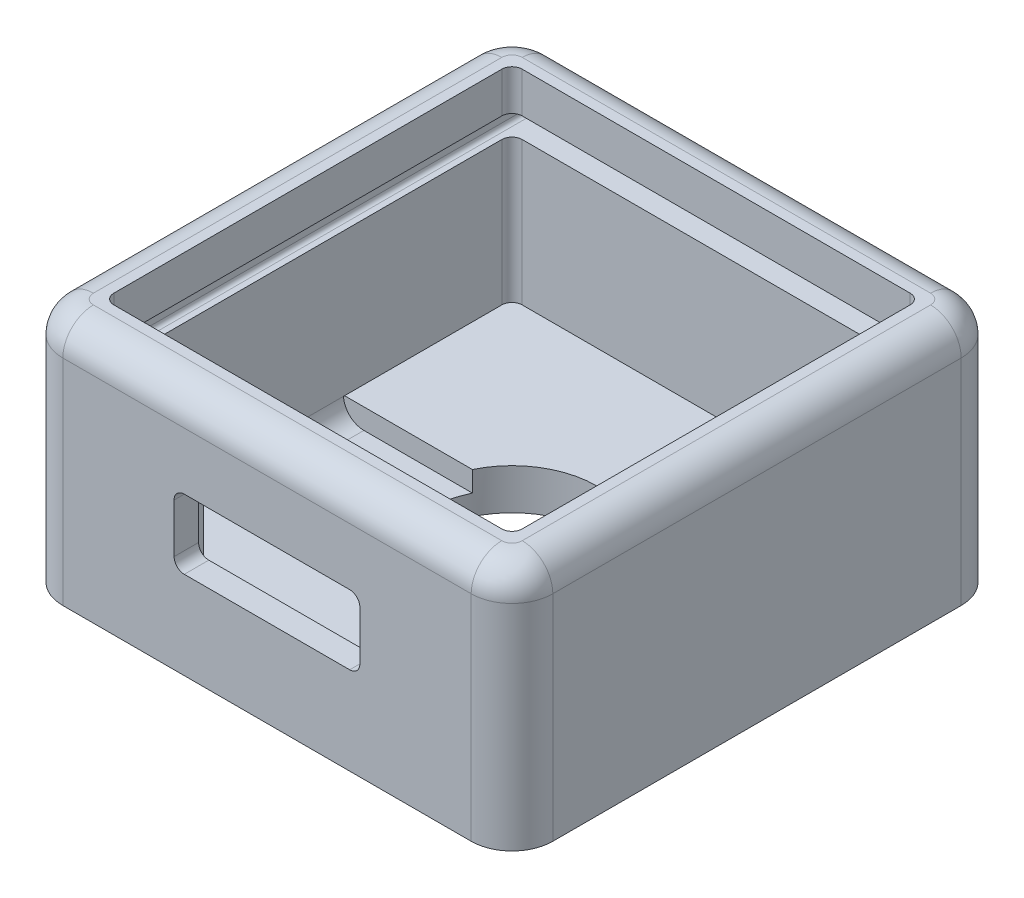
SolidWorks part; units mm, degrees
ref_plane "Front Plane" through (0, 0, 0) normal (0, 0, 1) x (1, 0, 0)
ref_plane "Top Plane" through (0, 0, 0) normal (0, 1, 0) x (1, 0, 0)
ref_plane "Right Plane" through (0, 0, 0) normal (1, 0, 0) x (0, 0, -1)
sketch "Sketch2" plane through (0, 0, 0) normal (0, 1, 0) x (1, 0, 0)
  line L1 (-10, -12) -> (10, -12)
  line L2 (-12, -10) -> (-12, 10)
  line L3 (-10, 12) -> (10, 12)
  line L4 (12, -10) -> (12, 10)
  line L5 (-12, -12) -> (12, 12) construction
  line L6 (-12, 12) -> (12, -12) construction
  arc A0 (-10, -12) -> (-12, -10) centre (-10, -10) cw
  arc A1 (10, -12) -> (12, -10) centre (10, -10) ccw
  arc A2 (10, 12) -> (12, 10) centre (10, 10) cw
  arc A3 (-12, 10) -> (-10, 12) centre (-10, 10) cw
  point P0 (0, 0)
  dimension "D3" = 2
  dimension "D1" = 24
  dimension "D2" = 24
extrude "Boss-Extrude2" add sketch "Sketch2" along normal blind 2
sketch "Sketch3" plane through (0, 2, 0) normal (0, 1, 0) x (1, 0, 0)
  line L1 (-9.5, -10) -> (9.5, -10)
  line L2 (-10, -9.5) -> (-10, 9.5)
  line L3 (-9.5, 10) -> (9.5, 10)
  line L4 (10, -9.5) -> (10, 9.5)
  line L5 (-10, -10) -> (10, 10) construction
  line L6 (-10, 10) -> (10, -10) construction
  line L7 (-10, -12) -> (10, -12)
  line L8 (-12, -10) -> (-12, 10)
  line L9 (-10, 12) -> (10, 12)
  line L10 (12, -10) -> (12, 10)
  line L11 (-12, -12) -> (12, 12) construction
  line L12 (-12, 12) -> (12, -12) construction
  arc A0 (9.5, -10) -> (10, -9.5) centre (9.5, -9.5) ccw
  arc A1 (-9.5, -10) -> (-10, -9.5) centre (-9.5, -9.5) cw
  arc A2 (9.5, 10) -> (10, 9.5) centre (9.5, 9.5) cw
  arc A3 (-10, 9.5) -> (-9.5, 10) centre (-9.5, 9.5) cw
  arc A4 (10, -12) -> (12, -10) centre (10, -10) ccw
  arc A5 (-10, -12) -> (-12, -10) centre (-10, -10) cw
  arc A6 (10, 12) -> (12, 10) centre (10, 10) cw
  arc A7 (-12, 10) -> (-10, 12) centre (-10, 10) cw
  point P0 (0, 0)
  point P18 (0, 0)
  dimension "D3" = 0.5
  dimension "D6" = 2
  dimension "D1" = 20
  dimension "D2" = 20
  dimension "D4" = 24
  dimension "D5" = 24
extrude "Boss-Extrude3" add sketch "Sketch3" along normal blind 10 contours A7 L9 A6 L10 A4 L7 A5 L8 | A3 L2 A1 L1 A0 L4 A2 L3
sketch "Sketch4" plane through (0, 0, 12) normal (0, 0, 1) x (1, 0, 0)
  line L0 (0, 0) -> (0, 12) construction
  line L1 (-4.05, 7.7) -> (4.05, 7.7)
  line L2 (-4.55, 7.2) -> (-4.55, 4.8)
  line L3 (-4.05, 4.3) -> (4.05, 4.3)
  line L4 (4.55, 7.2) -> (4.55, 4.8)
  line L5 (-4.55, 7.7) -> (4.55, 4.3) construction
  line L6 (-4.55, 4.3) -> (4.55, 7.7) construction
  line L7 (-10, 0) -> (10, 0) construction
  line L8 (-10, 12) -> (10, 12) construction
  arc A0 (-4.55, 4.8) -> (-4.05, 4.3) centre (-4.05, 4.8) ccw
  arc A1 (4.05, 4.3) -> (4.55, 4.8) centre (4.05, 4.8) ccw
  arc A2 (4.05, 7.7) -> (4.55, 7.2) centre (4.05, 7.2) cw
  arc A3 (-4.05, 7.7) -> (-4.55, 7.2) centre (-4.05, 7.2) ccw
  point P0 (0, 6)
  point P23 (0, 0)
  point P24 (0, 6)
  dimension "D3" = 0.5
  dimension "D1" = 9.1
  dimension "D2" = 3.4
extrude "Cut-Extrude1" cut sketch "Sketch4" against normal up to next contours L2 A0 L3 A1 L4 A2 L1 A3
sketch "Sketch5" plane through (0, 2, 0) normal (0, 1, 0) x (1, 0, 0)
  circle A0 centre (0, 0) radius 4.15
  dimension "D1" = 8.3
extrude "Cut-Extrude2" cut sketch "Sketch5" against normal up to next
sketch "Sketch6" plane through (0, 2, 0) normal (0, 1, 0) x (1, 0, 0)
  line L0 (-10, 0) -> (10, 0) construction
  line L1 (-10, -9.5) -> (-10, 9.5) construction
  line L2 (10, -9.5) -> (10, 9.5) construction
  line L4 (-10.0543, 1.8) -> (9.9457, 1.8)
  line L5 (-10.0543, 1.8) -> (-10.0543, -1.8)
  line L6 (-10.0543, -1.8) -> (9.9457, -1.8)
  line L7 (9.9457, 1.8) -> (9.9457, -1.8)
  line L8 (-10.0543, 1.8) -> (9.9457, -1.8) construction
  line L9 (-10.0543, -1.8) -> (9.9457, 1.8) construction
  point P6 (-0.0543, 0)
  point P11 (0, 0)
  dimension "D1" = 3.6
  dimension "D2" = 20
extrude "Cut-Extrude3" cut sketch "Sketch6" against normal blind 1
fillet "Fillet1" radius 1 2 edges at (9.9457, 1, 0) (-10.0543, 1, 0)
sketch "Sketch7" plane through (0, 0, 10) normal (0, 0, -1) x (-1, 0, 0)
  line L0 (4.05, 4.3) -> (-4.05, 4.3) construction
  line L1 (-5.11, 3.3) -> (5.11, 3.3)
  line L2 (-5.11, 3.3) -> (-5.11, 4.3)
  line L3 (-5.11, 4.3) -> (5.11, 4.3)
  line L4 (5.11, 3.3) -> (5.11, 4.3)
  line L5 (-5.11, 3.3) -> (5.11, 4.3) construction
  line L6 (-5.11, 4.3) -> (5.11, 3.3) construction
  line L7 (0, 4.3) -> (0, 2) construction
  line L8 (9.5, 2) -> (-9.5, 2) construction
  line L10 (-5.11, 8.26) -> (5.11, 8.26)
  line L11 (-5.11, 8.26) -> (-5.11, 4.3)
  line L12 (-5.11, 4.3) -> (5.11, 4.3)
  line L13 (5.11, 8.26) -> (5.11, 4.3)
  line L14 (-5.11, 8.26) -> (5.11, 4.3) construction
  line L15 (-5.11, 4.3) -> (5.11, 8.26) construction
  line L16 (4.05, 7.7) -> (-4.05, 7.7) construction
  point P0 (0, 3.8)
  point P12 (0, 6.28)
  line M10 (4.55, 7.2) -> (4.55, 4.8)
  arc M11 (4.55, 4.8) -> (4.05, 4.3) centre (4.05, 4.8) cw
  line M12 (4.05, 4.3) -> (-4.05, 4.3)
  arc M13 (-4.05, 4.3) -> (-4.55, 4.8) centre (-4.05, 4.8) cw
  line M14 (-4.55, 4.8) -> (-4.55, 7.2)
  arc M15 (-4.55, 7.2) -> (-4.05, 7.7) centre (-4.05, 7.2) cw
  line M16 (-4.05, 7.7) -> (4.05, 7.7)
  arc M17 (4.05, 7.7) -> (4.55, 7.2) centre (4.05, 7.2) cw
  dimension "D1" = 1
  dimension "D2" = 10.22
  dimension "D3" = 0.56
extrude "Cut-Extrude4" cut sketch "Sketch7" against normal blind 0.8 contours L13 L10 L11 L3 M13 M14 M15 M16 M17 M10 M11 | L1 L4 L3 L2 M12 region at (0, 3.8, 10) region at (5.0004, 6.28, 10)
sketch "Sketch8" plane through (0, 2, 0) normal (0, 1, 0) x (1, 0, 0)
  line L0 (0, -10) -> (0, 10) construction
  line L1 (-6, -4.15) -> (6, -4.15)
  line L2 (-6, -4.15) -> (-6, -5.3232)
  line L3 (-6, -5.3232) -> (6, -5.3232)
  line L4 (6, -4.15) -> (6, -5.3232)
  line L5 (-6, -4.15) -> (6, -5.3232) construction
  line L6 (-6, -5.3232) -> (6, -4.15) construction
  line L7 (-9.5, -10) -> (9.5, -10) construction
  line L8 (-9.5, 10) -> (9.5, 10) construction
  arc A0 (-3.7393, -1.8) -> (3.7393, -1.8) centre (0, 0) ccw construction
  point P0 (0, -4.7366)
  point P11 (0, 0)
  dimension "D1" = 12
extrude "Boss-Extrude4" add sketch "Sketch8" along normal blind 1.3
sketch "Sketch10" plane through (0, 3.3, 0) normal (0, 1, 0) x (1, 0, 0)
  line L0 (6, -5.3232) -> (5.31, -5.3232)
  line L1 (-6, -4.15) -> (-5.31, -4.15)
  line L2 (-6, -4.15) -> (-6, -5.3232)
  line L3 (-6, -5.3232) -> (-5.31, -5.3232)
  line L4 (-5.31, -4.15) -> (-5.31, -5.3232)
  line L5 (-6, -4.15) -> (-5.31, -5.3232) construction
  line L6 (-6, -5.3232) -> (-5.31, -4.15) construction
  line L7 (-6, -5.3232) -> (6, -5.3232) construction
  line L8 (-6, -4.15) -> (-6, -5.3232) construction
  line L9 (6, -4.15) -> (-6, -4.15) construction
  line L10 (0, -4.15) -> (0, -5.3232) construction
  line L11 (5.31, -4.15) -> (5.31, -5.3232)
  line L12 (6, -4.15) -> (5.31, -4.15)
  line L13 (6, -4.15) -> (6, -5.3232)
  point P0 (-5.655, -4.7366)
  dimension "D1" = 0.69
extrude "Boss-Extrude5" add sketch "Sketch10" along normal blind 2
fillet "Fillet2" radius 0.5 2 edges at (5.31, 3.3, 4.7366) (-5.31, 3.3, 4.7366)
fillet "Fillet6" radius 0.5 2 edges at (6, 2, 4.7366) (-6, 2, 4.7366)
sketch "Sketch13" [suppressed] plane through (0, 0, 0) normal (0, 0, 1) x (1, 0, 0)
  line L2 (-12, 12) -> (-12, 13)
  line L3 (-10, 12) -> (-10, 2) construction
  line L4 (-12, 12) -> (-12, 0) construction
  line L5 (-11, 14) -> (-9, 14)
  line L6 (-9, 14) -> (-9, 13)
  line L8 (-10, 12) -> (-9, 12)
  line L9 (-12, 12) -> (-12, 11.5)
  line L10 (-12, 11.5) -> (-9, 11.5)
  line L11 (-9, 12) -> (-9, 11.5)
  arc A0 (-12, 13) -> (-11, 14) centre (-11, 13) cw
  spline S0 degree 3 poles (-10, 12) (-10, 12.2913) (-9.9111, 12.6573) (-9.459, 13.006) (-9, 13) knots 0 0 0 0 0.483993 1 1 1 1
  point P2 (0, 0)
  point P3 (0, 0)
  point P14 (-12, 14)
  point P15 (0, 11.75)
  point P20 (0, 0)
  point P21 (0, 0)
  point P22 (0, 0)
  dimension "D2" = 1
  dimension "D1" = 2
  dimension "D3" = 1
  dimension "D4" = 0.5
  dimension "D5" = 1
fillet "Fillet8" radius 1.5 8 edges at (-11.4142, 12, -11.4142) (-12, 12, 0) (-11.4142, 12, 11.4142) (0, 12, 12) (11.4142, 12, 11.4142) (12, 12, 0) (11.4142, 12, -11.4142) (0, 12, -12)
sketch "Sketch21" plane through (0, 0, -12) normal (0, 0, -1) x (-1, 0, 0)
  line L0 (0, 10.5) -> (0, 0) construction
  line L1 (-10.3, 10.0166) -> (10.3, 10.0166)
  line L2 (-10.5, 9.8166) -> (-10.5, 9.2166)
  line L3 (-10.3, 9.0166) -> (10.3, 9.0166)
  line L4 (10.5, 9.8166) -> (10.5, 9.2166)
  line L5 (-10.5, 10.0166) -> (10.5, 9.0166) construction
  line L6 (-10.5, 9.0166) -> (10.5, 10.0166) construction
  line L7 (10, 10.5) -> (-10, 10.5) construction
  arc A0 (10.3, 9.0166) -> (10.5, 9.2166) centre (10.3, 9.2166) ccw
  arc A1 (10.3, 10.0166) -> (10.5, 9.8166) centre (10.3, 9.8166) cw
  arc A2 (-10.5, 9.2166) -> (-10.3, 9.0166) centre (-10.3, 9.2166) ccw
  arc A3 (-10.3, 10.0166) -> (-10.5, 9.8166) centre (-10.3, 9.8166) ccw
  point P0 (0, 9.5166)
  point P10 (0, 0)
  dimension "D2" = 0.2
  dimension "D1" = 21
  dimension "D3" = 1
extrude "Cut-Extrude6" cut sketch "Sketch21" against normal blind 22.5
fillet "Fillet9" radius 0.2 8 edges at (10.4414, 9.0752, 10.5) (10.5, 9.5166, 10.5) (10.4414, 9.958, 10.5) (0, 10.0166, 10.5) (-10.4414, 9.958, 10.5) (-10.5, 9.5166, 10.5) (-10.4414, 9.0752, 10.5) (0, 9.0166, 10.5)
